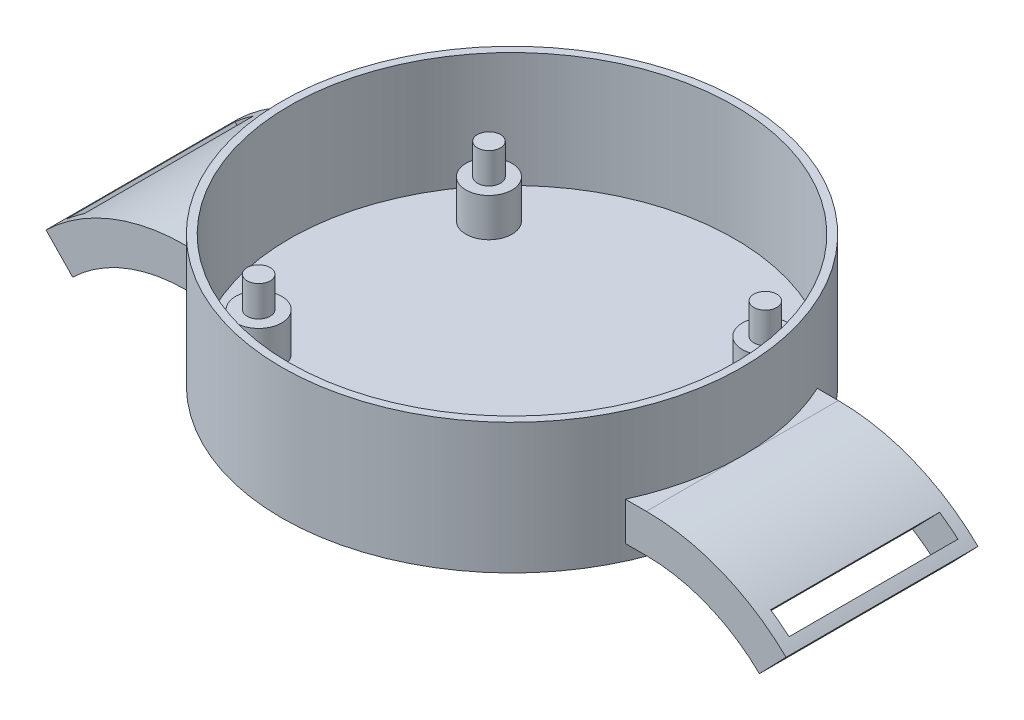
SolidWorks part; units mm, degrees
ref_plane "Front Plane" through (0, 0, 0) normal (0, 0, 1) x (1, 0, 0)
ref_plane "Top Plane" through (0, 0, 0) normal (0, 1, 0) x (1, 0, 0)
ref_plane "Right Plane" through (0, 0, 0) normal (1, 0, 0) x (0, 0, -1)
sketch "Sketch1" plane through (0, 0, 0) normal (0, 1, 0) x (1, 0, 0)
  circle A0 centre (0, 0) radius 30
extrude "Boss-Extrude1" add sketch "Sketch1" along normal blind 17
sketch "Sketch2" plane through (0, 17, 0) normal (0, 1, 0) x (1, 0, 0)
  circle A0 centre (0, 0) radius 29
extrude "Cut-Extrude1" cut sketch "Sketch2" against normal blind 15
sketch "Sketch3" plane through (0, 2, 0) normal (0, 1, 0) x (1, 0, 0)
  circle A0 centre (-18, 15) radius 3
  circle A1 centre (-18, -15) radius 3
  circle A2 centre (18, -15) radius 3
  circle A3 centre (18, 15) radius 3
  point P0 (0, 0)
extrude "Boss-Extrude5" add sketch "Sketch3" along normal blind 5
sketch "Sketch4" plane through (0, 7, 0) normal (0, 1, 0) x (1, 0, 0)
  circle A1 centre (-18, 15) radius 1.5
  circle A2 centre (-18, -15) radius 1.5
  circle A3 centre (18, 15) radius 1.5
  circle A4 centre (18, -15) radius 1.5
extrude "Boss-Extrude6" add sketch "Sketch4" along normal blind 4
ref_plane "Plane1" through (-30, 0, 0) normal (-1, 0, 0) x (0, 0, 1)
sketch "Sketch6" plane through (-30, 0, 0) normal (-1, 0, 0) x (0, 0, 1)
  line L0 (-30, 0) -> (30, 0) construction
  line L1 (-12.5, 7) -> (12.5, 7)
  line L2 (-12.5, 7) -> (-12.5, 2)
  line L3 (-12.5, 2) -> (12.5, 2)
  line L4 (12.5, 7) -> (12.5, 2)
  line L5 (-12.5, 7) -> (12.5, 2) construction
  line L6 (-12.5, 2) -> (12.5, 7) construction
  point P0 (0, 4.5)
  point P8 (0, 0)
  dimension "D1" = 25
  dimension "D2" = 5
  dimension "D3" = 2
  dimension "D4" = 12.5
sketch "Sketch7" plane through (0, 0, 0) normal (0, 0, 1) x (1, 0, 0)
  line L0 (-30, 2) -> (-30, 7) construction
  line L1 (-30, 4.5) -> (-17.5787, 4.5) construction
  arc A0 (-30, 4.5) -> (-46.4617, -2.1565) centre (-30, -19.1835) ccw
  point P3 (-45.5972, -1.9797)
  point P7 (-45.9092, -3.3152)
  point P8 (-45.42, 0)
  point P9 (0, 0)
  point P10 (0, 0)
  point P11 (0, 0)
  point P12 (-46.4617, -2.1565)
extrude "Boss-Extrude7" add sketch "Sketch6" against normal up to surface (2.7282 mm away) contours L1 L4 L3 L2 up to face at (0, 17, 30)
sketch "Sketch9" plane through (-30, 0, 0) normal (-1, 0, 0) x (0, 0, 1)
  line L1 (-12.5, 7) -> (12.5, 7)
  line L2 (-12.5, 7) -> (-12.5, 2)
  line L3 (-12.5, 2) -> (12.5, 2)
  line L4 (12.5, 7) -> (12.5, 2)
sweep "Sweep1" add profiles "Sketch9" path "Sketch7"
ref_plane "Plane2" through (-23.1068, 23.9004, 0) normal (-0.6951, 0.7189, 0) x (0.7189, 0.6951, 0)
sketch "Sketch10" plane through (-23.1068, 23.9004, 0) normal (-0.6951, 0.7189, 0) x (0.7189, 0.6951, 0)
  line L0 (-34.9021, -12.5) -> (-16.7027, -12.5) construction
  line L1 (-33.4021, -11) -> (-30.4021, -11)
  line L2 (-33.4021, -11) -> (-33.4021, 11)
  line L3 (-33.4021, 11) -> (-30.4021, 11)
  line L4 (-30.4021, -11) -> (-30.4021, 11)
  line L5 (-34.9021, -12.5) -> (-34.9021, 12.5) construction
  dimension "D1" = 22
  dimension "D2" = 1.5
  dimension "D3" = 1.5
  dimension "D4" = 3
extrude "Cut-Extrude2" cut sketch "Sketch10" against normal blind 10
pattern_circular "CirPattern1" count 2 every 180 about axis through (0, 17, 0) along (0, 1, 0) of "Sweep1", "Boss-Extrude7", "Cut-Extrude2"
